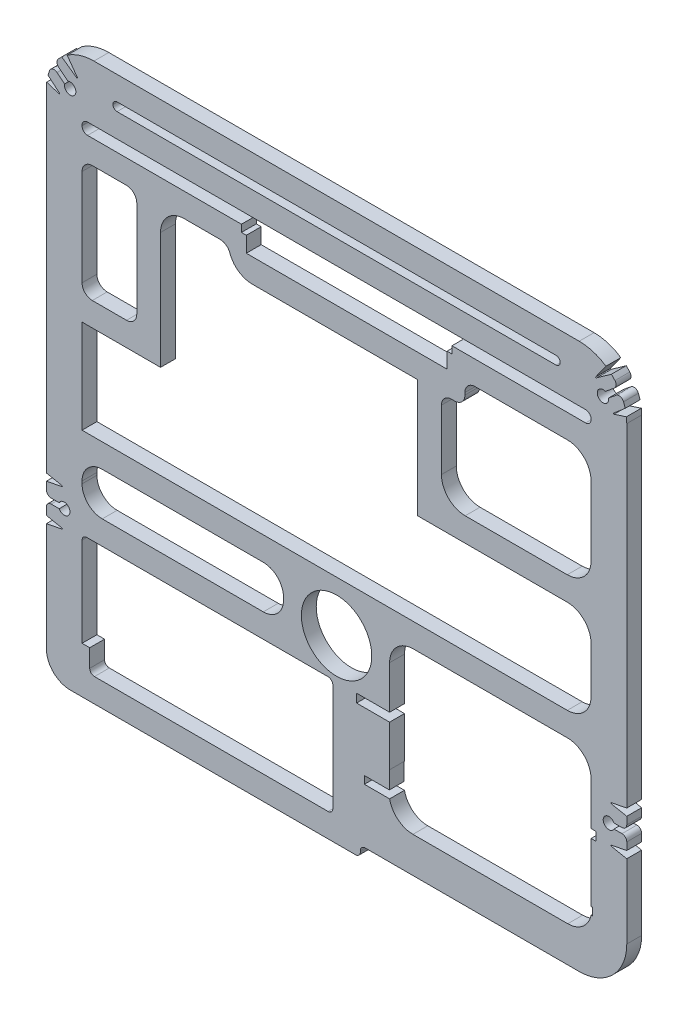
SolidWorks part; units mm, degrees
ref_plane "Front Plane" through (0, 0, 0) normal (0, 0, 1) x (1, 0, 0)
ref_plane "Top Plane" through (0, 0, 0) normal (0, 1, 0) x (1, 0, 0)
ref_plane "Right Plane" through (0, 0, 0) normal (1, 0, 0) x (0, 0, -1)
sketch "Sketch1" plane through (0, 0, 0) normal (0, 0, 1) x (1, 0, 0)
  line L0 (63.9883, 61.406) -> (63.9883, 57.596) construction
  line L1 (11.1776, 3.1158) -> (73.1542, 3.1158)
  line L2 (11.1776, 3.1158) -> (11.1776, 61.406)
  line L3 (11.1776, 61.406) -> (73.1542, 61.406)
  line L4 (73.1542, 3.1158) -> (73.1542, 61.406)
  line L5 (69.3442, 57.596) -> (14.9876, 57.596)
  line L6 (69.3442, 57.596) -> (69.3442, 6.9258)
  line L7 (69.3442, 6.9258) -> (14.9876, 6.9258)
  line L8 (14.9876, 57.596) -> (14.9876, 6.9258)
  line L9 (63.9883, 59.501) -> (18.0707, 59.501) construction
  line L10 (14.9876, 39.3805) -> (11.1776, 39.3805) construction
  line L11 (13.0826, 39.3805) -> (13.0826, 23.9527) construction
  line L12 (13.5248, 6.9258) -> (13.5248, 3.1158) construction
  line L13 (13.5248, 5.0208) -> (21.1598, 5.0208) construction
  line L14 (73.1542, 38.1916) -> (69.3442, 38.1916) construction
  line L15 (71.2492, 38.1916) -> (71.2492, 22.3321) construction
  line L16 (55.7422, 59.501) -> (30.5962, 59.501) construction
  line L19 (42.3087, 5.0208) -> (41.7626, 5.0208) construction
  line L21 (69.3442, 16.9588) -> (69.3442, 52.516) construction
  line L22 (14.9876, 47.563) -> (14.9876, 12.0058) construction
  dimension "D1" = 3.81
  dimension "D2" = 3.81
extrude "Boss-Extrude1" add sketch "Sketch1" along normal blind 1.5875
sketch "Sketch2" plane through (0, 0, 0) normal (0, 0, -1) x (-1, 0, 0)
  line L0 (-69.3442, 6.9258) -> (-69.3442, 57.596) construction
  line L1 (-69.3442, 26.6348) -> (-14.9876, 26.6348)
  line L2 (-69.3442, 26.6348) -> (-69.3442, 24.0948)
  line L3 (-69.3442, 24.0948) -> (-14.9876, 24.0948)
  line L4 (-14.9876, 26.6348) -> (-14.9876, 24.0948)
  line L5 (-14.9876, 57.596) -> (-14.9876, 6.9258) construction
  line L6 (-20.1206, 26.6348) -> (-57.8206, 26.6348) construction
  line L7 (-53.9642, 53.4304) -> (-53.9642, 51.7667)
  line L8 (-32.5266, 53.4304) -> (-32.0059, 53.4304)
  line L9 (-32.5266, 51.7667) -> (-53.9642, 51.7667) construction
  line L10 (-32.5266, 51.7667) -> (-32.5266, 53.4304) construction
  line L11 (-69.3442, 54.1924) -> (-54.4849, 54.1924)
  line L12 (-69.3442, 54.1924) -> (-69.3442, 51.6524)
  line L13 (-69.3442, 51.6524) -> (-55.8692, 51.6524)
  line L14 (-14.9876, 54.1924) -> (-14.9876, 51.6524)
  line L15 (-69.3442, 57.596) -> (-14.9876, 57.596)
  line L16 (-69.3442, 57.596) -> (-69.3442, 55.4243)
  line L17 (-69.3442, 55.4243) -> (-14.9876, 55.4243)
  line L18 (-14.9876, 57.596) -> (-14.9876, 55.4243)
  line L19 (-69.3442, 57.596) -> (-14.9876, 57.596) construction
  line L20 (-54.4849, 54.1924) -> (-54.4849, 53.4304)
  line L21 (-62.3462, 55.4243) -> (-23.9922, 55.4243) construction
  line L22 (-54.4849, 53.4304) -> (-53.9642, 53.4304)
  line L23 (-32.5266, 51.7667) -> (-53.9642, 51.7667)
  line L24 (-32.5266, 51.7667) -> (-32.5266, 53.4304)
  line L25 (-55.8692, 51.6524) -> (-55.8692, 49.2267)
  line L26 (-55.8692, 49.2267) -> (-30.6216, 49.2267)
  line L27 (-30.6216, 49.2267) -> (-30.6216, 51.6524)
  line L28 (-30.6216, 51.6524) -> (-14.9876, 51.6524)
  line L29 (-32.0059, 53.4304) -> (-32.0059, 54.1924)
  line L30 (-62.3462, 54.1924) -> (-23.9922, 54.1924) construction
  line L32 (-54.4849, 53.4304) -> (-54.4849, 54.1924) construction
  line L33 (-32.0059, 53.4304) -> (-54.4849, 53.4304) construction
  line L34 (-32.0059, 54.1924) -> (-14.9876, 54.1924)
  line L36 (-32.0059, 53.4304) -> (-32.0059, 54.1924) construction
  line L37 (-32.5266, 51.7667) -> (-32.5266, 53.4304) construction
  dimension "D1" = 2.54
  dimension "D2" = 1.905
  dimension "D3" = 2.54
  dimension "D4" = 1.905
  dimension "D5" = 2.54
extrude "Boss-Extrude2" add sketch "Sketch2" against normal up to surface (1.5875 mm away) up to face at (42.1659, 32.2609, 1.5875)
sketch "Sketch3" plane through (0, 0, 0) normal (0, 0, -1) x (-1, 0, 0)
  line L0 (-57.8206, 36.6348) -> (-50.8206, 36.6348) construction
  line L1 (-57.8206, 36.6348) -> (-50.8206, 36.6348)
  line L2 (-57.8206, 36.6348) -> (-69.3442, 36.6348)
  line L3 (-69.3442, 26.6348) -> (-69.3442, 51.6524) construction
  line L4 (-69.3442, 36.6348) -> (-69.3442, 39.1748)
  line L5 (-69.3442, 39.1748) -> (-53.3606, 39.1748)
  line L6 (-50.8206, 28.408) -> (-50.8206, 36.6348)
  line L7 (-50.8206, 28.408) -> (-50.8206, 49.2267)
  line L8 (-55.8692, 49.2267) -> (-30.6216, 49.2267) construction
  line L9 (-50.8206, 49.2267) -> (-53.3606, 49.2267)
  line L10 (-53.3606, 49.2267) -> (-53.3606, 39.1748)
  line L11 (-23.3706, 36.6348) -> (-20.1206, 36.6348) construction
  line L12 (-23.3706, 36.6348) -> (-20.1206, 36.6348)
  line L13 (-20.1206, 36.6348) -> (-14.9876, 36.6348)
  line L14 (-14.9876, 51.6524) -> (-14.9876, 26.6348) construction
  line L15 (-14.9876, 36.6348) -> (-14.9876, 39.1748)
  line L16 (-14.9876, 39.1748) -> (-20.8306, 39.1748)
  line L17 (-20.8306, 39.1748) -> (-20.8306, 51.6524)
  line L18 (-30.6216, 51.6524) -> (-14.9876, 51.6524) construction
  line L19 (-20.8306, 51.6524) -> (-23.3706, 51.6524)
  line L20 (-23.3706, 51.6524) -> (-23.3706, 36.6348)
  line L21 (-23.3706, 36.6348) -> (-16.2412, 25.8471)
  line M22 (-69.3442, 26.6348) -> (-69.3442, 51.6524)
  line M25 (-55.8692, 49.2267) -> (-30.6216, 49.2267)
  line M27 (-30.6216, 51.6524) -> (-14.9876, 51.6524)
  line M28 (-14.9876, 51.6524) -> (-14.9876, 26.6348)
  dimension "D1" = 2.54
  dimension "D2" = 2.54
  dimension "D3" = 2.54
  dimension "D4" = 2.54
extrude "Boss-Extrude3" add sketch "Sketch3" against normal up to surface (1.5875 mm away) contours L10 L5 L2 L1 L6 L7 M25 M22 | L20 L12 L13 L16 L17 M27 M28 region at (63.5824, 36.8588, 0) region at (20.9265, 42.3962, 0) up to face at (42.8855, 53.7395, 1.5875)
sketch "Sketch4" plane through (0, 0, 0) normal (0, 0, -1) x (-1, 0, 0)
  line L0 (-69.3442, 24.0948) -> (-14.9876, 24.0948) construction
  line L1 (-47.8301, 24.0948) -> (-36.5017, 24.0948)
  line L2 (-47.8301, 24.0948) -> (-47.8301, 6.9258)
  line L3 (-47.8301, 6.9258) -> (-36.5017, 6.9258)
  line L4 (-36.5017, 24.0948) -> (-36.5017, 6.9258)
  line L5 (-14.9876, 6.9258) -> (-69.3442, 6.9258) construction
  line L6 (-45.9251, 21.2246) -> (-47.8301, 21.2246) construction
  line L7 (-38.4067, 21.2246) -> (-36.5017, 21.2246) construction
  circle A0 centre (-42.1659, 21.2246) radius 3.7592 construction
  dimension "D1" = 1.905
extrude "Boss-Extrude4" add sketch "Sketch4" against normal up to surface (1.5875 mm away) up to face at (17.9091, 45.4136, 1.5875)
sketch "Sketch5" plane through (0, 0, 0) normal (0, 0, -1) x (-1, 0, 0)
  line L0 (-15.8038, 16.9715) -> (-41.7626, 16.9715) construction
  line L3 (-41.7626, 4.5128) -> (-41.7626, 16.9715) construction
  line L4 (-15.8038, 4.5128) -> (-41.7626, 4.5128) construction
  line L5 (-15.8038, 4.5128) -> (-15.8038, 16.9715) construction
  line L6 (-15.8038, 16.9715) -> (-41.7626, 16.9715)
  line L7 (-41.7626, 4.5128) -> (-41.7626, 16.9715)
  line L8 (-15.8038, 4.5128) -> (-41.7626, 4.5128)
  line L9 (-15.8038, 4.5128) -> (-15.8038, 16.9715)
  circle A0 centre (-42.1659, 21.2246) radius 3.7592 construction
  circle A1 centre (-42.1659, 21.2246) radius 3.7592
extrude "Cut-Extrude1" cut sketch "Sketch5" against normal up to surface (1.5875 mm away) up to face at (58.5871, 15.5103, 1.5875)
sketch "Sketch8" plane through (0, 0, 0) normal (0, 0, -1) x (-1, 0, 0)
  line L1 (-36.5017, 16.9715) -> (-14.9876, 16.9715)
  line L2 (-36.5017, 16.9715) -> (-36.5017, 19.5115)
  line L3 (-36.5017, 19.5115) -> (-14.9876, 19.5115)
  line L4 (-14.9876, 16.9715) -> (-14.9876, 19.5115)
  line L5 (-14.9876, 24.0948) -> (-14.9876, 6.9258) construction
  dimension "D1" = 2.54
extrude "Boss-Extrude5" add sketch "Sketch8" against normal up to surface (1.5875 mm away) up to face at (38.4067, 21.2246, 1.5875)
fillet "Fillet1" radius 5.08 3 edges at (73.1542, 3.1158, 0.7937) (11.1776, 61.406, 0.7937) (73.1542, 61.406, 0.7937)
fillet "Fillet2" radius 2.54 7 edges at (23.3706, 51.6524, 0.7937) (30.6216, 49.2267, 0.7937) (69.3442, 51.6524, 0.7937) (53.3606, 39.1748, 0.7937) (69.3442, 26.6348, 0.7937) (69.3442, 39.1748, 0.7937) (69.3442, 36.6348, 0.7937)
fillet "Fillet3" radius 1.0922 8 edges at (53.3606, 49.2267, 0.7937) (55.8692, 49.2267, 0.7937) (55.8692, 51.6524, 0.7937) (14.9876, 39.1748, 0.7937) (20.8306, 39.1748, 0.7937) (14.9876, 51.6524, 0.7937) (20.8306, 51.6524, 0.7937) (30.6216, 51.6524, 0.7937)
fillet "Fillet4" radius 0.5842 4 edges at (14.9876, 55.4243, 0.7937) (69.3442, 55.4243, 0.7937) (69.3442, 54.1924, 0.7937) (14.9876, 54.1924, 0.7937)
fillet "Fillet8" radius 2.159 4 edges at (36.5017, 19.5115, 0.7937) (36.5017, 24.0948, 0.7937) (14.9876, 24.0948, 0.7938) (14.9876, 19.5115, 0.7937)
sketch "Sketch6" plane through (0, 0, 0) normal (0, 0, -1) x (-1, 0, 0)
  line L0 (-16.6206, 28.1348) -> (-18.1206, 26.6348) construction
  line L1 (-18.1206, 36.6348) -> (-16.6206, 35.1348) construction
  line L2 (-16.6206, 35.1348) -> (-16.6206, 28.1348) construction
  line L3 (-16.6206, 28.1348) -> (-18.1206, 26.6348)
  line L4 (-18.1206, 36.6348) -> (-16.6206, 35.1348)
  line L5 (-16.6206, 35.1348) -> (-16.6206, 28.1348)
  line L6 (-18.1206, 36.6348) -> (-18.1206, 26.6348)
  circle A0 centre (-71.2492, 18.4306) radius 0.6096 construction
  circle A1 centre (-71.2492, 18.4306) radius 0.6096
  circle A4 centre (-70.6142, 57.596) radius 0.6096 construction
  circle A5 centre (-70.6142, 57.596) radius 0.6096
  circle A6 centre (-13.0826, 18.4306) radius 0.6096 construction
  circle A7 centre (-13.0826, 18.4306) radius 0.6096
  circle A10 centre (-13.7176, 57.596) radius 0.6096 construction
  circle A11 centre (-13.7176, 57.596) radius 0.6096
extrude "Cut-Extrude2" cut sketch "Sketch6" against normal up to surface (1.5875 mm away) up to face at (24.1846, 9.4701, 1.5875)
sketch "Sketch7" plane through (0, 0, 0) normal (0, 0, -1) x (-1, 0, 0)
  line L0 (-44.3026, 16.9715) -> (-69.8804, 16.9715) construction
  line L1 (-69.8804, 16.9715) -> (-69.8804, 16.0571) construction
  line L2 (-69.8804, 16.0571) -> (-44.3026, 16.0571) construction
  line L3 (-44.3026, 16.0571) -> (-44.3026, 16.9715) construction
  line L4 (-45.1366, 9.7751) -> (-69.5206, 9.7751) construction
  line L5 (-69.5206, 9.7751) -> (-69.5206, 8.9623) construction
  line L6 (-69.5206, 8.9623) -> (-45.1366, 8.9623) construction
  line L7 (-45.1366, 8.9623) -> (-45.1366, 9.7751) construction
  line L8 (-44.3026, 16.9715) -> (-69.8804, 16.9715)
  line L9 (-69.8804, 16.9715) -> (-69.8804, 16.0571)
  line L10 (-69.8804, 16.0571) -> (-44.3026, 16.0571)
  line L11 (-44.3026, 16.0571) -> (-44.3026, 16.9715)
  line L12 (-45.1366, 9.7751) -> (-69.5206, 9.7751)
  line L13 (-69.5206, 9.7751) -> (-69.5206, 8.9623)
  line L14 (-69.5206, 8.9623) -> (-45.1366, 8.9623)
  line L15 (-45.1366, 8.9623) -> (-45.1366, 9.7751)
  line L20 (-66.8536, 9.7751) -> (-47.8036, 9.7751)
  line L21 (-47.8036, 9.7751) -> (-47.8036, 11.6547)
  line L22 (-47.8036, 11.6547) -> (-66.8536, 11.6547)
  line L23 (-66.8536, 11.6547) -> (-66.8536, 9.7751)
  line L24 (-66.8536, 9.7751) -> (-47.8036, 9.7751)
  line L25 (-47.8036, 9.7751) -> (-47.8036, 11.6547)
  line L26 (-47.8036, 11.6547) -> (-66.8536, 11.6547)
  line L27 (-66.8536, 11.6547) -> (-66.8536, 9.7751)
  dimension "D1" = 0
extrude "Cut-Extrude3" cut sketch "Sketch7" against normal up to surface (1.5875 mm away) contours L14 L15 L12 L13 | L26 L27 L12 L25 | L10 L11 L8 L9 region at (57.0915, 16.5143, 0) region at (57.3286, 9.3687, 0) region at (57.3286, 10.7149, 0) up to face at (13.108, 57.596, 1.5875)
fillet "Fillet6" radius 0.508 4 edges at (41.7626, 16.9715, 0.7937) (41.7626, 4.5128, 0.7937) (15.8038, 4.5128, 0.7937) (14.9876, 16.9715, 0.7937)
sketch "Sketch9" plane through (0, 0, 1.5875) normal (0, 0, 1) x (1, 0, 0)
  line L0 (68.0742, 61.406) -> (16.2576, 61.406) construction
  line L1 (18.2896, 58.866) -> (66.0422, 58.866)
  line L2 (18.2896, 58.866) -> (18.2896, 57.9643)
  line L3 (18.2896, 57.9643) -> (66.0422, 57.9643)
  line L8 (66.0422, 58.866) -> (66.0422, 57.9643)
  line L9 (15.5718, 55.4243) -> (68.76, 55.4243) construction
  line L10 (11.1776, 56.326) -> (11.1776, 59.3208) construction
  line L11 (18.2896, 58.866) -> (11.1776, 58.866) construction
  line L13 (66.0422, 58.866) -> (73.1542, 58.866) construction
  line L14 (73.1542, 56.326) -> (73.1542, 56.8419) construction
  dimension "D1" = 2.54
  dimension "D2" = 2.54
  dimension "D3" = 7.112
extrude "Cut-Extrude4" cut sketch "Sketch9" against normal up to surface (1.5875 mm away) up to face at (57.106, 13.2916, 0)
fillet "Fillet7" radius 0.4318 4 edges at (18.2896, 57.9643, 0.7937) (18.2896, 58.866, 0.7937) (66.0422, 57.9643, 0.7937) (66.0422, 58.866, 0.7937)
fillet "Fillet9" radius 2.54 4 edges at (69.3442, 6.9258, 0.7937) (47.8301, 6.9258, 0.7937) (69.3442, 24.0948, 0.7937) (47.8301, 24.0948, 0.7937)
sketch "Sketch10" plane through (0, 0, 1.5875) normal (0, 0, 1) x (1, 0, 0)
  line L0 (42.1659, 24.9838) -> (42.1659, -13.4858) construction
  line L1 (11.1776, 3.1158) -> (44.7059, 3.1158)
  line L2 (11.1776, 3.1158) -> (11.1776, 1.9728)
  line L3 (11.1776, 1.9728) -> (44.7059, 1.9728)
  line L4 (44.7059, 3.1158) -> (44.7059, 1.9728)
  line L5 (16.3118, 4.5128) -> (41.2546, 4.5128) construction
  circle A0 centre (42.1659, 21.2246) radius 3.7592 construction
  dimension "D1" = 2.54
  dimension "D2" = 2.54
extrude "Boss-Extrude6" add sketch "Sketch10" against normal up to surface (1.5875 mm away) up to face at (42.1659, 58.4152, 0)
fillet "Fillet10" radius 2.54 1 edges at (11.1776, 1.9728, 0.7937)
fillet "Fillet11" radius 0.508 2 edges at (44.7059, 3.1158, 0.7937) (44.7059, 1.9728, 0.7937)
sketch "Sketch11" plane through (0, 0, 1.5875) normal (0, 0, 1) x (1, 0, 0)
  line L0 (14.486, 59.0031) -> (13.3987, 60.5253) construction
  line L1 (12.8232, 60.0693) -> (14.4151, 58.9322) construction
  line L2 (13.4744, 58.155) -> (12.501, 58.9492) construction
  line L3 (12.3178, 58.3774) -> (13.1211, 57.7221) construction
  line L4 (12.5786, 56.6017) -> (11.3522, 57.6466) construction
  line L5 (11.2145, 56.9374) -> (12.5302, 56.5147) construction
  line L6 (69.8457, 59.0031) -> (70.933, 60.5253) construction
  line L7 (71.5085, 60.0693) -> (69.9166, 58.9322) construction
  line L8 (70.8574, 58.155) -> (71.8308, 58.9492) construction
  line L9 (72.0139, 58.3774) -> (71.2106, 57.7221) construction
  line L10 (71.7531, 56.6017) -> (72.9795, 57.6466) construction
  line L11 (73.1172, 56.9374) -> (71.8016, 56.5147) construction
  line L12 (71.4982, 20.4444) -> (73.1542, 20.7756) construction
  line L13 (73.1542, 20.0136) -> (71.4982, 20.3448) construction
  line L14 (71.791, 18.71) -> (72.6462, 18.71) construction
  line L15 (72.6462, 18.1512) -> (71.791, 18.1512) construction
  line L16 (71.4982, 16.5165) -> (73.1542, 16.8477) construction
  line L17 (73.1542, 16.0857) -> (71.4982, 16.4169) construction
  line L18 (14.486, 59.0031) -> (13.3987, 60.5253)
  line L19 (12.8232, 60.0693) -> (14.4151, 58.9322)
  line L20 (13.4744, 58.155) -> (12.501, 58.9492)
  line L21 (12.3178, 58.3774) -> (13.1211, 57.7221)
  line L22 (12.5786, 56.6017) -> (11.3522, 57.6466)
  line L23 (11.2145, 56.9374) -> (12.5302, 56.5147)
  line L24 (69.8457, 59.0031) -> (70.933, 60.5253)
  line L25 (71.5085, 60.0693) -> (69.9166, 58.9322)
  line L26 (70.8574, 58.155) -> (71.8308, 58.9492)
  line L27 (72.0139, 58.3774) -> (71.2106, 57.7221)
  line L28 (71.7531, 56.6017) -> (72.9795, 57.6466)
  line L29 (73.1172, 56.9374) -> (71.8016, 56.5147)
  line L30 (71.4982, 20.4444) -> (73.1542, 20.7756)
  line L31 (73.1542, 20.0136) -> (71.4982, 20.3448)
  line L32 (71.791, 18.71) -> (72.6462, 18.71)
  line L33 (72.6462, 18.1512) -> (71.791, 18.1512)
  line L34 (71.4982, 16.5165) -> (73.1542, 16.8477)
  line L35 (73.1542, 16.0857) -> (71.4982, 16.4169)
  line L36 (12.8335, 20.4444) -> (11.1776, 20.7756) construction
  line L37 (11.1776, 20.0136) -> (12.8335, 20.3448) construction
  line L38 (12.5408, 18.71) -> (11.6856, 18.71) construction
  line L39 (11.6856, 18.1512) -> (12.5408, 18.1512) construction
  line L40 (12.8335, 16.5165) -> (11.1776, 16.8477) construction
  line L41 (11.1776, 16.0857) -> (12.8335, 16.4169) construction
  line L42 (12.8335, 20.4444) -> (11.1776, 20.7756)
  line L43 (11.1776, 20.0136) -> (12.8335, 20.3448)
  line L44 (12.5408, 18.71) -> (11.6856, 18.71)
  line L45 (11.6856, 18.1512) -> (12.5408, 18.1512)
  line L46 (12.8335, 16.5165) -> (11.1776, 16.8477)
  line L47 (11.1776, 16.0857) -> (12.8335, 16.4169)
  line L48 (11.1776, 56.326) -> (11.1776, 4.5128) construction
  line L49 (73.1542, 8.1958) -> (73.1542, 56.326) construction
  line L50 (11.1776, 20.7756) -> (11.1776, 20.0136)
  line L51 (73.1542, 16.0857) -> (73.1542, 16.8477)
  line L52 (73.1542, 17.6432) -> (73.1542, 19.218)
  line L53 (73.1542, 20.0136) -> (73.1542, 20.7756)
  line L54 (11.1776, 19.218) -> (11.1776, 17.6432)
  line L55 (11.1776, 16.8477) -> (11.1776, 16.0857)
  arc A0 (14.4151, 58.9322) -> (14.486, 59.0031) centre (14.4446, 58.9736) ccw construction
  arc A1 (12.4404, 59.678) -> (12.501, 58.9492) centre (12.8221, 59.3428) ccw construction
  arc A2 (12.3178, 58.3774) -> (11.5233, 58.168) centre (11.9967, 57.9838) ccw construction
  arc A3 (12.5302, 56.5147) -> (12.5786, 56.6017) centre (12.5457, 56.5631) ccw construction
  arc A4 (69.8457, 59.0031) -> (69.9166, 58.9322) centre (69.8871, 58.9736) ccw construction
  arc A5 (71.8308, 58.9492) -> (71.8913, 59.678) centre (71.5096, 59.3428) ccw construction
  arc A6 (72.8085, 58.168) -> (72.0139, 58.3774) centre (72.335, 57.9838) ccw construction
  arc A7 (71.7531, 56.6017) -> (71.8016, 56.5147) centre (71.786, 56.5631) ccw construction
  arc A8 (71.4982, 20.4444) -> (71.4982, 20.3448) centre (71.5082, 20.3946) ccw construction
  arc A9 (72.6462, 18.71) -> (73.1542, 19.218) centre (72.6462, 19.218) ccw construction
  arc A10 (73.1542, 17.6432) -> (72.6462, 18.1512) centre (72.6462, 17.6432) ccw construction
  arc A11 (71.4982, 16.5165) -> (71.4982, 16.4169) centre (71.5082, 16.4667) ccw construction
  arc A12 (14.4151, 58.9322) -> (14.486, 59.0031) centre (14.4446, 58.9736) ccw
  arc A13 (12.4404, 59.678) -> (12.501, 58.9492) centre (12.8221, 59.3428) ccw
  arc A14 (12.3178, 58.3774) -> (11.5233, 58.168) centre (11.9967, 57.9838) ccw
  arc A15 (12.5302, 56.5147) -> (12.5786, 56.6017) centre (12.5457, 56.5631) ccw
  arc A16 (69.8457, 59.0031) -> (69.9166, 58.9322) centre (69.8871, 58.9736) ccw
  arc A17 (71.8308, 58.9492) -> (71.8913, 59.678) centre (71.5096, 59.3428) ccw
  arc A18 (72.8085, 58.168) -> (72.0139, 58.3774) centre (72.335, 57.9838) ccw
  arc A19 (71.7531, 56.6017) -> (71.8016, 56.5147) centre (71.786, 56.5631) ccw
  arc A20 (71.4982, 20.4444) -> (71.4982, 20.3448) centre (71.5082, 20.3946) ccw
  arc A21 (72.6462, 18.71) -> (73.1542, 19.218) centre (72.6462, 19.218) ccw
  arc A22 (73.1542, 17.6432) -> (72.6462, 18.1512) centre (72.6462, 17.6432) ccw
  arc A23 (71.4982, 16.5165) -> (71.4982, 16.4169) centre (71.5082, 16.4667) ccw
  arc A24 (12.8335, 20.3448) -> (12.8335, 20.4444) centre (12.8235, 20.3946) ccw construction
  arc A25 (11.1776, 19.218) -> (11.6856, 18.71) centre (11.6856, 19.218) ccw construction
  arc A26 (11.6856, 18.1512) -> (11.1776, 17.6432) centre (11.6856, 17.6432) ccw construction
  arc A27 (12.8335, 16.4169) -> (12.8335, 16.5165) centre (12.8235, 16.4667) ccw construction
  arc A28 (12.8335, 20.3448) -> (12.8335, 20.4444) centre (12.8235, 20.3946) ccw
  arc A29 (11.1776, 19.218) -> (11.6856, 18.71) centre (11.6856, 19.218) ccw
  arc A30 (11.6856, 18.1512) -> (11.1776, 17.6432) centre (11.6856, 17.6432) ccw
  arc A31 (12.8335, 16.4169) -> (12.8335, 16.5165) centre (12.8235, 16.4667) ccw
  circle A32 centre (13.0826, 18.4306) radius 0.6096 construction
  arc A33 (16.2576, 61.406) -> (11.1776, 56.326) centre (16.2576, 56.326) ccw construction
  circle A34 centre (13.7176, 57.596) radius 0.6096 construction
  arc A35 (73.1542, 56.326) -> (68.0742, 61.406) centre (68.0742, 56.326) ccw construction
  circle A36 centre (70.6142, 57.596) radius 0.6096 construction
  circle A37 centre (71.2492, 18.4306) radius 0.6096 construction
  arc A38 (12.5408, 18.71) -> (12.5408, 18.1512) centre (13.0826, 18.4306) ccw
  arc A39 (13.3987, 60.5253) -> (12.8232, 60.0693) centre (16.2576, 56.326) ccw
  arc A40 (13.4744, 58.155) -> (13.1211, 57.7221) centre (13.7176, 57.596) ccw
  arc A41 (73.1172, 56.9374) -> (72.9795, 57.6466) centre (68.0742, 56.326) ccw
  arc A42 (71.2106, 57.7221) -> (70.8574, 58.155) centre (70.6142, 57.596) ccw
  arc A43 (71.791, 18.1512) -> (71.791, 18.71) centre (71.2492, 18.4306) ccw
  arc A44 (72.8085, 58.168) -> (71.8913, 59.678) centre (68.0742, 56.326) ccw
  arc A45 (71.5085, 60.0693) -> (70.933, 60.5253) centre (68.0742, 56.326) ccw
  arc A46 (12.4404, 59.678) -> (11.5233, 58.168) centre (16.2576, 56.326) ccw
  arc A47 (11.3522, 57.6466) -> (11.2145, 56.9374) centre (16.2576, 56.326) ccw
extrude "Cut-Extrude5" cut sketch "Sketch11" against normal through all
